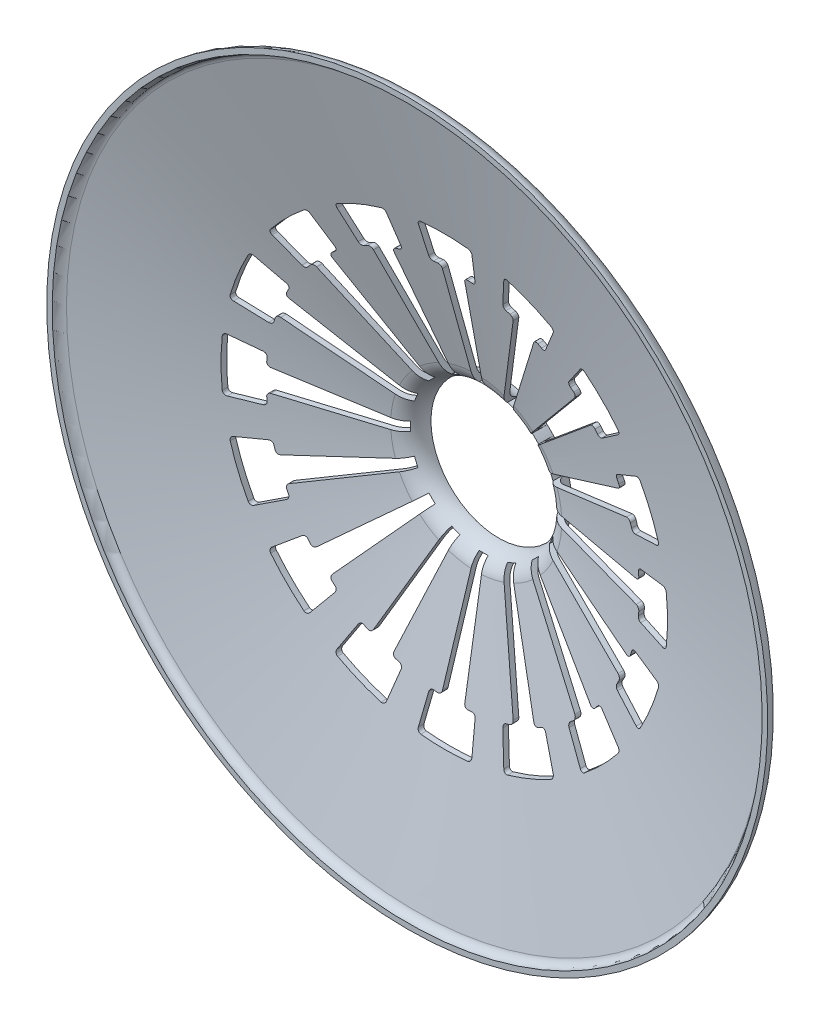
SolidWorks part; units mm, degrees
material "Plain Carbon Steel"
ref_plane "Front Plane" through (0, 0, 0) normal (0, 0, 1) x (1, 0, 0)
ref_plane "Top Plane" through (0, 0, 0) normal (0, 1, 0) x (1, 0, 0)
ref_plane "Right Plane" through (0, 0, 0) normal (1, 0, 0) x (0, 0, -1)
sketch "Sketch1" plane through (0, 0, 0) normal (1, 0, 0) x (0, 0, -1)
  line L0 (0, 18.5) -> (0, 97)
  line L1 (0, 175.3491) -> (0, -175.3491) construction
  line L2 (2.1726, 95.2741) -> (18.8669, 23.3723)
  line L3 (25, 18.5) -> (25, 0) construction
  line L4 (25, 0) -> (0, 0) construction
  line L5 (3.6337, 95.6133) -> (20.328, 23.7115)
  line L6 (25, 18.5) -> (25, 20)
  line L7 (0, 98.5) -> (0, 97)
  line L8 (25, 18.5) -> (0, 18.5)
  circle A0 centre (0, 94.7697) radius 2.2303 construction
  arc A1 (2.1726, 95.2741) -> (0, 97) centre (0, 94.7697) ccw
  circle A2 centre (25, 24.7963) radius 6.2963 construction
  arc A3 (25, 18.5) -> (18.8669, 23.3723) centre (25, 24.7963) cw
  arc A4 (3.6337, 95.6133) -> (0, 98.5) centre (0, 94.7697) ccw
  circle A5 centre (25, 24.7963) radius 4.7963 construction
  arc A6 (25, 20) -> (20.328, 23.7115) centre (25, 24.7963) cw
  point P6 (0, 0)
  point P7 (0, 0)
  dimension "D1" = 97
  dimension "D2" = 18.5
  dimension "D4" = 1.5
  dimension "D5" = 25
  dimension "D6" = 0
  dimension "D3" = 1.5
revolve "Revolve4" add sketch "Sketch1" angle 360 about L4 region at (0, 57.8681, -11.7246)
sketch "Sketch2" plane through (0, 0, -25) normal (0, 0, -1) x (-1, 0, 0)
  line L0 (-145.7601, 0) -> (145.7601, 0) construction
  line L1 (0, 130.2225) -> (0, -130.2225) construction
  line L2 (0, 0) -> (3.0518, 49.8968)
  line L3 (0, 0) -> (-3.0518, 49.8968)
  line L4 (6.336, 51.6029) -> (7.3111, 59.5445)
  line L5 (-6.336, 51.6029) -> (-7.3111, 59.5445)
  line L6 (0, 0) -> (21.9142, 44.9307)
  line L7 (0, 0) -> (16.2752, 47.2665)
  line L8 (13.8938, 50.0995) -> (16.0321, 57.8098)
  line L9 (25.6013, 45.2501) -> (29.5413, 52.2141)
  line L10 (0, 0) -> (37.4403, 33.1244)
  line L11 (0, 0) -> (33.1244, 37.4403)
  line L12 (32.0085, 40.969) -> (36.9346, 47.2741)
  line L13 (40.969, 32.0085) -> (47.2741, 36.9346)
  line L14 (0, 0) -> (47.2665, 16.2752)
  line L15 (0, 0) -> (44.9307, 21.9142)
  line L16 (45.2501, 25.6013) -> (52.2141, 29.5413)
  line L17 (50.0995, 13.8938) -> (57.8098, 16.0321)
  line L18 (0, 0) -> (49.8968, -3.0518)
  line L19 (0, 0) -> (49.8968, 3.0518)
  line L20 (51.6029, 6.336) -> (59.5445, 7.3111)
  line L21 (51.6029, -6.336) -> (59.5445, -7.3111)
  line L22 (0, 0) -> (44.9307, -21.9142)
  line L23 (0, 0) -> (47.2665, -16.2752)
  line L24 (50.0995, -13.8938) -> (57.8098, -16.0321)
  line L25 (45.2501, -25.6013) -> (52.2141, -29.5413)
  line L26 (0, 0) -> (33.1244, -37.4403)
  line L27 (0, 0) -> (37.4403, -33.1244)
  line L28 (40.969, -32.0085) -> (47.2741, -36.9346)
  line L29 (32.0085, -40.969) -> (36.9346, -47.2741)
  line L30 (0, 0) -> (16.2752, -47.2665)
  line L31 (0, 0) -> (21.9142, -44.9307)
  line L32 (25.6013, -45.2501) -> (29.5413, -52.2141)
  line L33 (13.8938, -50.0995) -> (16.0321, -57.8098)
  line L34 (0, 0) -> (-3.0518, -49.8968)
  line L35 (0, 0) -> (3.0518, -49.8968)
  line L36 (6.336, -51.6029) -> (7.3111, -59.5445)
  line L37 (-6.336, -51.6029) -> (-7.3111, -59.5445)
  line L38 (0, 0) -> (-21.9142, -44.9307)
  line L39 (0, 0) -> (-16.2752, -47.2665)
  line L40 (-13.8938, -50.0995) -> (-16.0321, -57.8098)
  line L41 (-25.6013, -45.2501) -> (-29.5413, -52.2141)
  line L42 (0, 0) -> (-37.4403, -33.1244)
  line L43 (0, 0) -> (-33.1244, -37.4403)
  line L44 (-32.0085, -40.969) -> (-36.9346, -47.2741)
  line L45 (-40.969, -32.0085) -> (-47.2741, -36.9346)
  line L46 (0, 0) -> (-47.2665, -16.2752)
  line L47 (0, 0) -> (-44.9307, -21.9142)
  line L48 (-45.2501, -25.6013) -> (-52.2141, -29.5413)
  line L49 (-50.0995, -13.8938) -> (-57.8098, -16.0321)
  line L50 (0, 0) -> (-49.8968, 3.0518)
  line L51 (0, 0) -> (-49.8968, -3.0518)
  line L52 (-51.6029, -6.336) -> (-59.5445, -7.3111)
  line L53 (-51.6029, 6.336) -> (-59.5445, 7.3111)
  line L54 (0, 0) -> (-44.9307, 21.9142)
  line L55 (0, 0) -> (-47.2665, 16.2752)
  line L56 (-50.0995, 13.8938) -> (-57.8098, 16.0321)
  line L57 (-45.2501, 25.6013) -> (-52.2141, 29.5413)
  line L58 (0, 0) -> (-33.1244, 37.4403)
  line L59 (0, 0) -> (-37.4403, 33.1244)
  line L60 (-40.969, 32.0085) -> (-47.2741, 36.9346)
  line L61 (-32.0085, 40.969) -> (-36.9346, 47.2741)
  line L62 (0, 0) -> (-16.2752, 47.2665)
  line L63 (0, 0) -> (-21.9142, 44.9307)
  line L64 (-25.6013, 45.2501) -> (-29.5413, 52.2141)
  line L65 (-13.8938, 50.0995) -> (-16.0321, 57.8098)
  circle A0 centre (0, 0) radius 51 construction
  circle A1 centre (0, 0) radius 61 construction
  arc A2 (6.4239, 60.6608) -> (-6.4239, 60.6608) centre (0, 0) ccw
  arc A3 (5.2407, 50.73) -> (4.131, 50.8324) centre (0, 0) ccw
  arc A4 (5.2407, 50.73) -> (6.336, 51.6029) centre (5.3435, 51.7247) ccw
  arc A5 (7.3111, 59.5445) -> (6.4239, 60.6608) centre (6.3186, 59.6664) ccw
  arc A6 (-6.4239, 60.6608) -> (-7.3111, 59.5445) centre (-6.3186, 59.6664) ccw
  arc A7 (-5.2407, 50.73) -> (-6.336, 51.6029) centre (-5.3435, 51.7247) cw
  arc A8 (-4.131, 50.8324) -> (-5.2407, 50.73) centre (0, 0) ccw
  arc A9 (3.0518, 49.8968) -> (4.131, 50.8324) centre (4.05, 49.8357) cw
  arc A10 (-3.0518, 49.8968) -> (-4.131, 50.8324) centre (-4.05, 49.8357) ccw
  arc A11 (24.2553, 44.8629) -> (23.2692, 45.3822) centre (0, 0) ccw
  arc A12 (21.9142, 44.9307) -> (23.2692, 45.3822) centre (22.813, 44.4923) cw
  arc A13 (16.2752, 47.2665) -> (15.6362, 48.5439) centre (15.3296, 47.592) ccw
  arc A14 (15.6362, 48.5439) -> (14.5717, 48.874) centre (0, 0) ccw
  arc A15 (14.5717, 48.874) -> (13.8938, 50.0995) centre (14.8575, 49.8323) cw
  arc A16 (17.279, 58.5016) -> (16.0321, 57.8098) centre (16.9957, 57.5426) ccw
  arc A17 (29.1488, 53.585) -> (17.279, 58.5016) centre (0, 0) ccw
  arc A18 (29.5413, 52.2141) -> (29.1488, 53.585) centre (28.671, 52.7065) ccw
  arc A19 (24.2553, 44.8629) -> (25.6013, 45.2501) centre (24.7309, 45.7426) ccw
  arc A20 (39.5773, 32.1658) -> (38.865, 33.0229) centre (0, 0) ccw
  arc A21 (37.4403, 33.1244) -> (38.865, 33.0229) centre (38.1029, 32.3754) cw
  arc A22 (33.1244, 37.4403) -> (33.0229, 38.865) centre (32.3754, 38.1029) ccw
  arc A23 (33.0229, 38.865) -> (32.1658, 39.5773) centre (0, 0) ccw
  arc A24 (32.1658, 39.5773) -> (32.0085, 40.969) centre (32.7965, 40.3533) cw
  arc A25 (38.3513, 47.4361) -> (36.9346, 47.2741) centre (37.7226, 46.6584) ccw
  arc A26 (47.4361, 38.3513) -> (38.3513, 47.4361) centre (0, 0) ccw
  arc A27 (47.2741, 36.9346) -> (47.4361, 38.3513) centre (46.6584, 37.7226) ccw
  arc A28 (39.5773, 32.1658) -> (40.969, 32.0085) centre (40.3533, 32.7965) ccw
  arc A29 (48.874, 14.5717) -> (48.5439, 15.6362) centre (0, 0) ccw
  arc A30 (47.2665, 16.2752) -> (48.5439, 15.6362) centre (47.592, 15.3296) cw
  arc A31 (44.9307, 21.9142) -> (45.3822, 23.2692) centre (44.4923, 22.813) ccw
  arc A32 (45.3822, 23.2692) -> (44.8629, 24.2553) centre (0, 0) ccw
  arc A33 (44.8629, 24.2553) -> (45.2501, 25.6013) centre (45.7426, 24.7309) cw
  arc A34 (53.585, 29.1488) -> (52.2141, 29.5413) centre (52.7065, 28.671) ccw
  arc A35 (58.5016, 17.279) -> (53.585, 29.1488) centre (0, 0) ccw
  arc A36 (57.8098, 16.0321) -> (58.5016, 17.279) centre (57.5426, 16.9957) ccw
  arc A37 (48.874, 14.5717) -> (50.0995, 13.8938) centre (49.8323, 14.8575) ccw
  arc A38 (50.73, -5.2407) -> (50.8324, -4.131) centre (0, 0) ccw
  arc A39 (49.8968, -3.0518) -> (50.8324, -4.131) centre (49.8357, -4.05) cw
  arc A40 (49.8968, 3.0518) -> (50.8324, 4.131) centre (49.8357, 4.05) ccw
  arc A41 (50.8324, 4.131) -> (50.73, 5.2407) centre (0, 0) ccw
  arc A42 (50.73, 5.2407) -> (51.6029, 6.336) centre (51.7247, 5.3435) cw
  arc A43 (60.6608, 6.4239) -> (59.5445, 7.3111) centre (59.6664, 6.3186) ccw
  arc A44 (60.6608, -6.4239) -> (60.6608, 6.4239) centre (0, 0) ccw
  arc A45 (59.5445, -7.3111) -> (60.6608, -6.4239) centre (59.6664, -6.3186) ccw
  arc A46 (50.73, -5.2407) -> (51.6029, -6.336) centre (51.7247, -5.3435) ccw
  arc A47 (44.8629, -24.2553) -> (45.3822, -23.2692) centre (0, 0) ccw
  arc A48 (44.9307, -21.9142) -> (45.3822, -23.2692) centre (44.4923, -22.813) cw
  arc A49 (47.2665, -16.2752) -> (48.5439, -15.6362) centre (47.592, -15.3296) ccw
  arc A50 (48.5439, -15.6362) -> (48.874, -14.5717) centre (0, 0) ccw
  arc A51 (48.874, -14.5717) -> (50.0995, -13.8938) centre (49.8323, -14.8575) cw
  arc A52 (58.5016, -17.279) -> (57.8098, -16.0321) centre (57.5426, -16.9957) ccw
  arc A53 (53.585, -29.1488) -> (58.5016, -17.279) centre (0, 0) ccw
  arc A54 (52.2141, -29.5413) -> (53.585, -29.1488) centre (52.7065, -28.671) ccw
  arc A55 (44.8629, -24.2553) -> (45.2501, -25.6013) centre (45.7426, -24.7309) ccw
  arc A56 (32.1658, -39.5773) -> (33.0229, -38.865) centre (0, 0) ccw
  arc A57 (33.1244, -37.4403) -> (33.0229, -38.865) centre (32.3754, -38.1029) cw
  arc A58 (37.4403, -33.1244) -> (38.865, -33.0229) centre (38.1029, -32.3754) ccw
  arc A59 (38.865, -33.0229) -> (39.5773, -32.1658) centre (0, 0) ccw
  arc A60 (39.5773, -32.1658) -> (40.969, -32.0085) centre (40.3533, -32.7965) cw
  arc A61 (47.4361, -38.3513) -> (47.2741, -36.9346) centre (46.6584, -37.7226) ccw
  arc A62 (38.3513, -47.4361) -> (47.4361, -38.3513) centre (0, 0) ccw
  arc A63 (36.9346, -47.2741) -> (38.3513, -47.4361) centre (37.7226, -46.6584) ccw
  arc A64 (32.1658, -39.5773) -> (32.0085, -40.969) centre (32.7965, -40.3533) ccw
  arc A65 (14.5717, -48.874) -> (15.6362, -48.5439) centre (0, 0) ccw
  arc A66 (16.2752, -47.2665) -> (15.6362, -48.5439) centre (15.3296, -47.592) cw
  arc A67 (21.9142, -44.9307) -> (23.2692, -45.3822) centre (22.813, -44.4923) ccw
  arc A68 (23.2692, -45.3822) -> (24.2553, -44.8629) centre (0, 0) ccw
  arc A69 (24.2553, -44.8629) -> (25.6013, -45.2501) centre (24.7309, -45.7426) cw
  arc A70 (29.1488, -53.585) -> (29.5413, -52.2141) centre (28.671, -52.7065) ccw
  arc A71 (17.279, -58.5016) -> (29.1488, -53.585) centre (0, 0) ccw
  arc A72 (16.0321, -57.8098) -> (17.279, -58.5016) centre (16.9957, -57.5426) ccw
  arc A73 (14.5717, -48.874) -> (13.8938, -50.0995) centre (14.8575, -49.8323) ccw
  arc A74 (-5.2407, -50.73) -> (-4.131, -50.8324) centre (0, 0) ccw
  arc A75 (-3.0518, -49.8968) -> (-4.131, -50.8324) centre (-4.05, -49.8357) cw
  arc A76 (3.0518, -49.8968) -> (4.131, -50.8324) centre (4.05, -49.8357) ccw
  arc A77 (4.131, -50.8324) -> (5.2407, -50.73) centre (0, 0) ccw
  arc A78 (5.2407, -50.73) -> (6.336, -51.6029) centre (5.3435, -51.7247) cw
  arc A79 (6.4239, -60.6608) -> (7.3111, -59.5445) centre (6.3186, -59.6664) ccw
  arc A80 (-6.4239, -60.6608) -> (6.4239, -60.6608) centre (0, 0) ccw
  arc A81 (-7.3111, -59.5445) -> (-6.4239, -60.6608) centre (-6.3186, -59.6664) ccw
  arc A82 (-5.2407, -50.73) -> (-6.336, -51.6029) centre (-5.3435, -51.7247) ccw
  arc A83 (-24.2553, -44.8629) -> (-23.2692, -45.3822) centre (0, 0) ccw
  arc A84 (-21.9142, -44.9307) -> (-23.2692, -45.3822) centre (-22.813, -44.4923) cw
  arc A85 (-16.2752, -47.2665) -> (-15.6362, -48.5439) centre (-15.3296, -47.592) ccw
  arc A86 (-15.6362, -48.5439) -> (-14.5717, -48.874) centre (0, 0) ccw
  arc A87 (-14.5717, -48.874) -> (-13.8938, -50.0995) centre (-14.8575, -49.8323) cw
  arc A88 (-17.279, -58.5016) -> (-16.0321, -57.8098) centre (-16.9957, -57.5426) ccw
  arc A89 (-29.1488, -53.585) -> (-17.279, -58.5016) centre (0, 0) ccw
  arc A90 (-29.5413, -52.2141) -> (-29.1488, -53.585) centre (-28.671, -52.7065) ccw
  arc A91 (-24.2553, -44.8629) -> (-25.6013, -45.2501) centre (-24.7309, -45.7426) ccw
  arc A92 (-39.5773, -32.1658) -> (-38.865, -33.0229) centre (0, 0) ccw
  arc A93 (-37.4403, -33.1244) -> (-38.865, -33.0229) centre (-38.1029, -32.3754) cw
  arc A94 (-33.1244, -37.4403) -> (-33.0229, -38.865) centre (-32.3754, -38.1029) ccw
  arc A95 (-33.0229, -38.865) -> (-32.1658, -39.5773) centre (0, 0) ccw
  arc A96 (-32.1658, -39.5773) -> (-32.0085, -40.969) centre (-32.7965, -40.3533) cw
  arc A97 (-38.3513, -47.4361) -> (-36.9346, -47.2741) centre (-37.7226, -46.6584) ccw
  arc A98 (-47.4361, -38.3513) -> (-38.3513, -47.4361) centre (0, 0) ccw
  arc A99 (-47.2741, -36.9346) -> (-47.4361, -38.3513) centre (-46.6584, -37.7226) ccw
  arc A100 (-39.5773, -32.1658) -> (-40.969, -32.0085) centre (-40.3533, -32.7965) ccw
  arc A101 (-48.874, -14.5717) -> (-48.5439, -15.6362) centre (0, 0) ccw
  arc A102 (-47.2665, -16.2752) -> (-48.5439, -15.6362) centre (-47.592, -15.3296) cw
  arc A103 (-44.9307, -21.9142) -> (-45.3822, -23.2692) centre (-44.4923, -22.813) ccw
  arc A104 (-45.3822, -23.2692) -> (-44.8629, -24.2553) centre (0, 0) ccw
  arc A105 (-44.8629, -24.2553) -> (-45.2501, -25.6013) centre (-45.7426, -24.7309) cw
  arc A106 (-53.585, -29.1488) -> (-52.2141, -29.5413) centre (-52.7065, -28.671) ccw
  arc A107 (-58.5016, -17.279) -> (-53.585, -29.1488) centre (0, 0) ccw
  arc A108 (-57.8098, -16.0321) -> (-58.5016, -17.279) centre (-57.5426, -16.9957) ccw
  arc A109 (-48.874, -14.5717) -> (-50.0995, -13.8938) centre (-49.8323, -14.8575) ccw
  arc A110 (-50.73, 5.2407) -> (-50.8324, 4.131) centre (0, 0) ccw
  arc A111 (-49.8968, 3.0518) -> (-50.8324, 4.131) centre (-49.8357, 4.05) cw
  arc A112 (-49.8968, -3.0518) -> (-50.8324, -4.131) centre (-49.8357, -4.05) ccw
  arc A113 (-50.8324, -4.131) -> (-50.73, -5.2407) centre (0, 0) ccw
  arc A114 (-50.73, -5.2407) -> (-51.6029, -6.336) centre (-51.7247, -5.3435) cw
  arc A115 (-60.6608, -6.4239) -> (-59.5445, -7.3111) centre (-59.6664, -6.3186) ccw
  arc A116 (-60.6608, 6.4239) -> (-60.6608, -6.4239) centre (0, 0) ccw
  arc A117 (-59.5445, 7.3111) -> (-60.6608, 6.4239) centre (-59.6664, 6.3186) ccw
  arc A118 (-50.73, 5.2407) -> (-51.6029, 6.336) centre (-51.7247, 5.3435) ccw
  arc A119 (-44.8629, 24.2553) -> (-45.3822, 23.2692) centre (0, 0) ccw
  arc A120 (-44.9307, 21.9142) -> (-45.3822, 23.2692) centre (-44.4923, 22.813) cw
  arc A121 (-47.2665, 16.2752) -> (-48.5439, 15.6362) centre (-47.592, 15.3296) ccw
  arc A122 (-48.5439, 15.6362) -> (-48.874, 14.5717) centre (0, 0) ccw
  arc A123 (-48.874, 14.5717) -> (-50.0995, 13.8938) centre (-49.8323, 14.8575) cw
  arc A124 (-58.5016, 17.279) -> (-57.8098, 16.0321) centre (-57.5426, 16.9957) ccw
  arc A125 (-53.585, 29.1488) -> (-58.5016, 17.279) centre (0, 0) ccw
  arc A126 (-52.2141, 29.5413) -> (-53.585, 29.1488) centre (-52.7065, 28.671) ccw
  arc A127 (-44.8629, 24.2553) -> (-45.2501, 25.6013) centre (-45.7426, 24.7309) ccw
  arc A128 (-32.1658, 39.5773) -> (-33.0229, 38.865) centre (0, 0) ccw
  arc A129 (-33.1244, 37.4403) -> (-33.0229, 38.865) centre (-32.3754, 38.1029) cw
  arc A130 (-37.4403, 33.1244) -> (-38.865, 33.0229) centre (-38.1029, 32.3754) ccw
  arc A131 (-38.865, 33.0229) -> (-39.5773, 32.1658) centre (0, 0) ccw
  arc A132 (-39.5773, 32.1658) -> (-40.969, 32.0085) centre (-40.3533, 32.7965) cw
  arc A133 (-47.4361, 38.3513) -> (-47.2741, 36.9346) centre (-46.6584, 37.7226) ccw
  arc A134 (-38.3513, 47.4361) -> (-47.4361, 38.3513) centre (0, 0) ccw
  arc A135 (-36.9346, 47.2741) -> (-38.3513, 47.4361) centre (-37.7226, 46.6584) ccw
  arc A136 (-32.1658, 39.5773) -> (-32.0085, 40.969) centre (-32.7965, 40.3533) ccw
  arc A137 (-14.5717, 48.874) -> (-15.6362, 48.5439) centre (0, 0) ccw
  arc A138 (-16.2752, 47.2665) -> (-15.6362, 48.5439) centre (-15.3296, 47.592) cw
  arc A139 (-21.9142, 44.9307) -> (-23.2692, 45.3822) centre (-22.813, 44.4923) ccw
  arc A140 (-23.2692, 45.3822) -> (-24.2553, 44.8629) centre (0, 0) ccw
  arc A141 (-24.2553, 44.8629) -> (-25.6013, 45.2501) centre (-24.7309, 45.7426) cw
  arc A142 (-29.1488, 53.585) -> (-29.5413, 52.2141) centre (-28.671, 52.7065) ccw
  arc A143 (-17.279, 58.5016) -> (-29.1488, 53.585) centre (0, 0) ccw
  arc A144 (-16.0321, 57.8098) -> (-17.279, 58.5016) centre (-16.9957, 57.5426) ccw
  arc A145 (-14.5717, 48.874) -> (-13.8938, 50.0995) centre (-14.8575, 49.8323) ccw
  point P6 (0, 0)
  point P10 (0, 0)
  point P22 (6.2153, 50.6199)
  point P25 (7.434, 60.5453)
  point P28 (-7.434, 60.5453)
  point P31 (-6.2153, 50.6199)
  point P34 (3.1135, 50.9049)
  point P37 (-3.1135, 50.9049)
  point P311 (0, 0)
  circle M6 centre (0, 0) radius 20
  dimension "D1" = 122
  dimension "D2" = 102
  dimension "D7" = 1
  dimension "D8" = 1
  dimension "D3" = 7
  dimension "D4" = 3.5
  dimension "D5" = 7
  dimension "D6" = 14
  dimension "D9" = 16
extrude "Cut-Extrude1" cut sketch "Sketch2" against normal through all contours A10 L3 L2 A9 A3 A4 L4 A5 A2 A6 L5 A7 A8 M6 | A11 A19 L9 A18 A17 A16 L8 A15 A14 A13 L7 L6 A12 M6 | A20 A28 L13 A27 A26 A25 L12 A24 A23 A22 L11 L10 A21 M6 | A29 A37 L17 A36 A35 A34 L16 A33 A32 A31 L15 L14 A30 M6 | A38 A46 L21 A45 A44 A43 L20 A42 A41 A40 L19 L18 A39 M6 | A47 A55 L25 A54 A53 A52 L24 A51 A50 A49 L23 L22 A48 M6 | A56 A64 L29 A63 A62 A61 L28 A60 A59 A58 L27 L26 A57 M6 | A65 A73 L33 A72 A71 A70 L32 A69 A68 A67 L31 L30 A66 M6 | A74 A82 L37 A81 A80 A79 L36 A78 A77 A76 L35 L34 A75 M6 | A83 A91 L41 A90 A89 A88 L40 A87 A86 A85 L39 L38 A84 M6 | A92 A100 L45 A99 A98 A97 L44 A96 A95 A94 L43 L42 A93 M6 | A101 A109 L49 A108 A107 A106 L48 A105 A104 A103 L47 L46 A102 M6 | A110 A118 L53 A117 A116 A115 L52 A114 A113 A112 L51 L50 A111 M6 | A119 A127 L57 A126 A125 A124 L56 A123 A122 A121 L55 L54 A120 M6 | A128 A136 L61 A135 A134 A133 L60 A132 A131 A130 L59 L58 A129 M6 | A137 A145 L65 A144 A143 A142 L64 A141 A140 A139 L63 L62 A138 M6 | L50 A111 A110 A118 L53 A117 A116 A115 L52 A114 A113 A112 L51 region at (0, 46.9293, -25) region at (-17.9591, 43.357, -25) region at (-33.184, 33.184, -25) region at (-43.357, 17.9591, -25) region at (-46.9293, 0, -25) region at (-43.357, -17.9591, -25) region at (-33.184, -33.184, -25) region at (-17.9591, -43.357, -25) region at (0, -46.9293, -25) region at (17.9591, -43.357, -25) region at (33.184, -33.184, -25) region at (43.357, -17.9591, -25) region at (46.9293, 0, -25) region at (43.357, 17.9591, -25) region at (33.184, 33.184, -25) region at (17.9591, 43.357, -25)
equation "\"a\"= 194"
equation "\"b\"= 37"
equation "\"c\"= 25"
equation "\"d\"= 14"
equation "\"e\"= 1"
equation "\"x\"= 1"
equation "\"y\"= 1"
equation "\"z\"= 1"
equation "\"D1@Sketch1\"=\"a\"/2"
equation "\"D2@Sketch1\"=\"b\"/2"
equation "\"D5@Sketch1\"=\"c\""
equation "\"D3@Sketch2\"=\"d\"/2"
equation "\"D4@Sketch2\"=\"d\"/4"
equation "\"D5@Sketch2\"=\"d\"/2"
equation "\"D6@Sketch2\"=\"d\""
